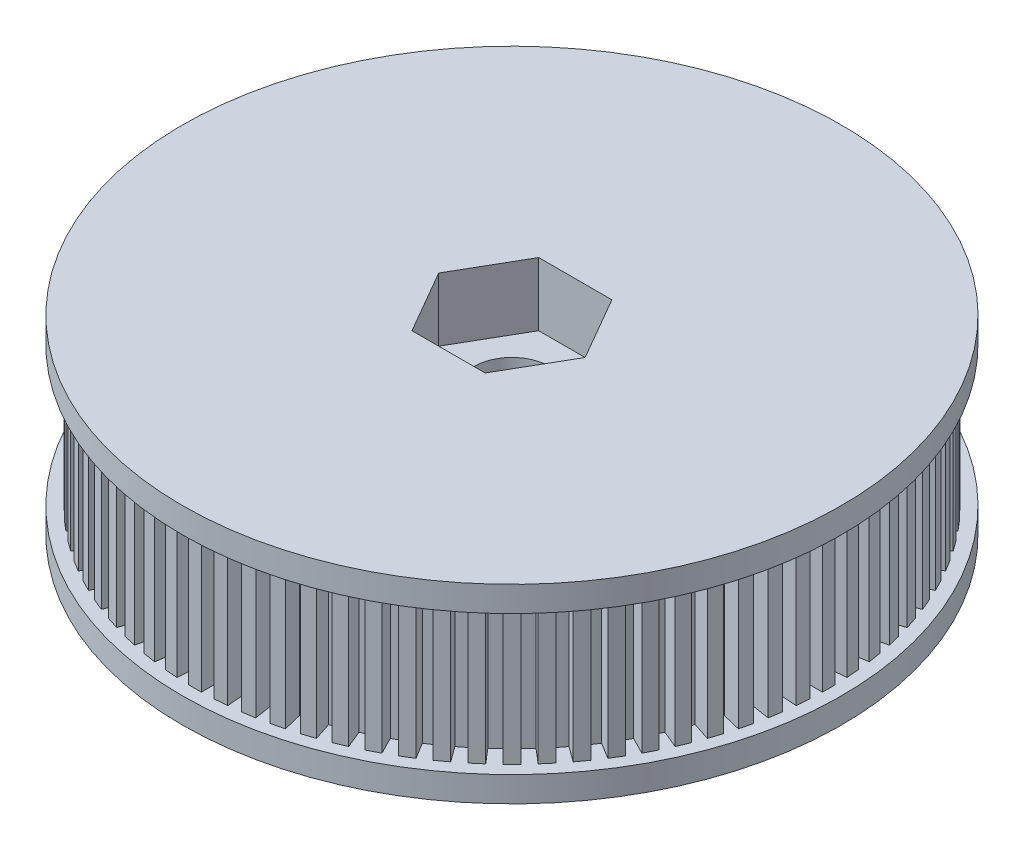
SolidWorks part; units mm, degrees
ref_plane "Front Plane" through (0, 0, 0) normal (0, 0, 1) x (1, 0, 0)
ref_plane "Top Plane" through (0, 0, 0) normal (0, 1, 0) x (1, 0, 0)
ref_plane "Right Plane" through (0, 0, 0) normal (1, 0, 0) x (0, 0, -1)
sketch "Sketch1" plane through (0, 0, 0) normal (0, 1, 0) x (1, 0, 0)
  line L0 (0, 39.6954) -> (0, -43.6583) construction
  line L1 (-0.5, 23.5) -> (-0.5, 25)
  line L2 (-0.5, 25) -> (0.5, 25)
  line L3 (0.5, 25) -> (0.5, 23.5)
  line L4 (1.3453, 23.4668) -> (1.463, 24.9622)
  line L5 (1.463, 24.9622) -> (2.4599, 24.8837)
  line L6 (2.4599, 24.8837) -> (2.3422, 23.3883)
  line L7 (3.1824, 23.2889) -> (3.417, 24.7704)
  line L8 (3.417, 24.7704) -> (4.4047, 24.614)
  line L9 (4.4047, 24.614) -> (4.1701, 23.1325)
  line L10 (4.9998, 22.9674) -> (5.3499, 24.426)
  line L11 (5.3499, 24.426) -> (6.3223, 24.1925)
  line L12 (6.3223, 24.1925) -> (5.9722, 22.734)
  line L13 (6.7864, 22.5043) -> (7.2499, 23.9309)
  line L14 (7.2499, 23.9309) -> (8.201, 23.6219)
  line L15 (8.201, 23.6219) -> (7.7374, 22.1953)
  line L16 (8.5311, 21.9025) -> (9.1051, 23.2883)
  line L17 (9.1051, 23.2883) -> (10.029, 22.9056)
  line L18 (10.029, 22.9056) -> (9.455, 21.5198)
  line L19 (10.2233, 21.1656) -> (10.9043, 22.5022)
  line L20 (10.9043, 22.5022) -> (11.7953, 22.0482)
  line L21 (11.7953, 22.0482) -> (11.1143, 20.7117)
  line L22 (11.8524, 20.2983) -> (12.6361, 21.5773)
  line L23 (12.6361, 21.5773) -> (13.4888, 21.0548)
  line L24 (13.4888, 21.0548) -> (12.705, 19.7758)
  line L25 (13.4084, 19.3058) -> (14.2901, 20.5193)
  line L26 (14.2901, 20.5193) -> (15.0991, 19.9315)
  line L27 (15.0991, 19.9315) -> (14.2175, 18.718)
  line L28 (14.8818, 18.1943) -> (15.856, 19.3349)
  line L29 (15.856, 19.3349) -> (16.6164, 18.6854)
  line L30 (16.6164, 18.6854) -> (15.6422, 17.5448)
  line L31 (16.2635, 16.9706) -> (17.3241, 18.0312)
  line L32 (17.3241, 18.0312) -> (18.0312, 17.3241)
  line L33 (18.0312, 17.3241) -> (16.9706, 16.2635)
  line L34 (17.5448, 15.6422) -> (18.6854, 16.6164)
  line L35 (18.6854, 16.6164) -> (19.3349, 15.856)
  line L36 (19.3349, 15.856) -> (18.1943, 14.8818)
  line L37 (18.718, 14.2175) -> (19.9315, 15.0991)
  line L38 (19.9315, 15.0991) -> (20.5193, 14.2901)
  line L39 (20.5193, 14.2901) -> (19.3058, 13.4084)
  line L40 (19.7758, 12.705) -> (21.0548, 13.4888)
  line L41 (21.0548, 13.4888) -> (21.5773, 12.6361)
  line L42 (21.5773, 12.6361) -> (20.2983, 11.8524)
  line L43 (20.7117, 11.1143) -> (22.0482, 11.7953)
  line L44 (22.0482, 11.7953) -> (22.5022, 10.9043)
  line L45 (22.5022, 10.9043) -> (21.1656, 10.2233)
  line L46 (21.5198, 9.455) -> (22.9056, 10.029)
  line L47 (22.9056, 10.029) -> (23.2883, 9.1051)
  line L48 (23.2883, 9.1051) -> (21.9025, 8.5311)
  line L49 (22.1953, 7.7374) -> (23.6219, 8.201)
  line L50 (23.6219, 8.201) -> (23.9309, 7.2499)
  line L51 (23.9309, 7.2499) -> (22.5043, 6.7864)
  line L52 (22.734, 5.9722) -> (24.1925, 6.3223)
  line L53 (24.1925, 6.3223) -> (24.426, 5.3499)
  line L54 (24.426, 5.3499) -> (22.9674, 4.9998)
  line L55 (23.1325, 4.1701) -> (24.614, 4.4047)
  line L56 (24.614, 4.4047) -> (24.7704, 3.417)
  line L57 (24.7704, 3.417) -> (23.2889, 3.1824)
  line L58 (23.3883, 2.3422) -> (24.8837, 2.4599)
  line L59 (24.8837, 2.4599) -> (24.9622, 1.463)
  line L60 (24.9622, 1.463) -> (23.4668, 1.3453)
  line L61 (23.5, 0.5) -> (25, 0.5)
  line L62 (25, 0.5) -> (25, -0.5)
  line L63 (25, -0.5) -> (23.5, -0.5)
  line L64 (23.4668, -1.3453) -> (24.9622, -1.463)
  line L65 (24.9622, -1.463) -> (24.8837, -2.4599)
  line L66 (24.8837, -2.4599) -> (23.3883, -2.3422)
  line L67 (23.2889, -3.1824) -> (24.7704, -3.417)
  line L68 (24.7704, -3.417) -> (24.614, -4.4047)
  line L69 (24.614, -4.4047) -> (23.1325, -4.1701)
  line L70 (22.9674, -4.9998) -> (24.426, -5.3499)
  line L71 (24.426, -5.3499) -> (24.1925, -6.3223)
  line L72 (24.1925, -6.3223) -> (22.734, -5.9722)
  line L73 (22.5043, -6.7864) -> (23.9309, -7.2499)
  line L74 (23.9309, -7.2499) -> (23.6219, -8.201)
  line L75 (23.6219, -8.201) -> (22.1953, -7.7374)
  line L76 (21.9025, -8.5311) -> (23.2883, -9.1051)
  line L77 (23.2883, -9.1051) -> (22.9056, -10.029)
  line L78 (22.9056, -10.029) -> (21.5198, -9.455)
  line L79 (21.1656, -10.2233) -> (22.5022, -10.9043)
  line L80 (22.5022, -10.9043) -> (22.0482, -11.7953)
  line L81 (22.0482, -11.7953) -> (20.7117, -11.1143)
  line L82 (20.2983, -11.8524) -> (21.5773, -12.6361)
  line L83 (21.5773, -12.6361) -> (21.0548, -13.4888)
  line L84 (21.0548, -13.4888) -> (19.7758, -12.705)
  line L85 (19.3058, -13.4084) -> (20.5193, -14.2901)
  line L86 (20.5193, -14.2901) -> (19.9315, -15.0991)
  line L87 (19.9315, -15.0991) -> (18.718, -14.2175)
  line L88 (18.1943, -14.8818) -> (19.3349, -15.856)
  line L89 (19.3349, -15.856) -> (18.6854, -16.6164)
  line L90 (18.6854, -16.6164) -> (17.5448, -15.6422)
  line L91 (16.9706, -16.2635) -> (18.0312, -17.3241)
  line L92 (18.0312, -17.3241) -> (17.3241, -18.0312)
  line L93 (17.3241, -18.0312) -> (16.2635, -16.9706)
  line L94 (15.6422, -17.5448) -> (16.6164, -18.6854)
  line L95 (16.6164, -18.6854) -> (15.856, -19.3349)
  line L96 (15.856, -19.3349) -> (14.8818, -18.1943)
  line L97 (14.2175, -18.718) -> (15.0991, -19.9315)
  line L98 (15.0991, -19.9315) -> (14.2901, -20.5193)
  line L99 (14.2901, -20.5193) -> (13.4084, -19.3058)
  line L100 (12.705, -19.7758) -> (13.4888, -21.0548)
  line L101 (13.4888, -21.0548) -> (12.6361, -21.5773)
  line L102 (12.6361, -21.5773) -> (11.8524, -20.2983)
  line L103 (11.1143, -20.7117) -> (11.7953, -22.0482)
  line L104 (11.7953, -22.0482) -> (10.9043, -22.5022)
  line L105 (10.9043, -22.5022) -> (10.2233, -21.1656)
  line L106 (9.455, -21.5198) -> (10.029, -22.9056)
  line L107 (10.029, -22.9056) -> (9.1051, -23.2883)
  line L108 (9.1051, -23.2883) -> (8.5311, -21.9025)
  line L109 (7.7374, -22.1953) -> (8.201, -23.6219)
  line L110 (8.201, -23.6219) -> (7.2499, -23.9309)
  line L111 (7.2499, -23.9309) -> (6.7864, -22.5043)
  line L112 (5.9722, -22.734) -> (6.3223, -24.1925)
  line L113 (6.3223, -24.1925) -> (5.3499, -24.426)
  line L114 (5.3499, -24.426) -> (4.9998, -22.9674)
  line L115 (4.1701, -23.1325) -> (4.4047, -24.614)
  line L116 (4.4047, -24.614) -> (3.417, -24.7704)
  line L117 (3.417, -24.7704) -> (3.1824, -23.2889)
  line L118 (2.3422, -23.3883) -> (2.4599, -24.8837)
  line L119 (2.4599, -24.8837) -> (1.463, -24.9622)
  line L120 (1.463, -24.9622) -> (1.3453, -23.4668)
  line L121 (0.5, -23.5) -> (0.5, -25)
  line L122 (0.5, -25) -> (-0.5, -25)
  line L123 (-0.5, -25) -> (-0.5, -23.5)
  line L124 (-1.3453, -23.4668) -> (-1.463, -24.9622)
  line L125 (-1.463, -24.9622) -> (-2.4599, -24.8837)
  line L126 (-2.4599, -24.8837) -> (-2.3422, -23.3883)
  line L127 (-3.1824, -23.2889) -> (-3.417, -24.7704)
  line L128 (-3.417, -24.7704) -> (-4.4047, -24.614)
  line L129 (-4.4047, -24.614) -> (-4.1701, -23.1325)
  line L130 (-4.9998, -22.9674) -> (-5.3499, -24.426)
  line L131 (-5.3499, -24.426) -> (-6.3223, -24.1925)
  line L132 (-6.3223, -24.1925) -> (-5.9722, -22.734)
  line L133 (-6.7864, -22.5043) -> (-7.2499, -23.9309)
  line L134 (-7.2499, -23.9309) -> (-8.201, -23.6219)
  line L135 (-8.201, -23.6219) -> (-7.7374, -22.1953)
  line L136 (-8.5311, -21.9025) -> (-9.1051, -23.2883)
  line L137 (-9.1051, -23.2883) -> (-10.029, -22.9056)
  line L138 (-10.029, -22.9056) -> (-9.455, -21.5198)
  line L139 (-10.2233, -21.1656) -> (-10.9043, -22.5022)
  line L140 (-10.9043, -22.5022) -> (-11.7953, -22.0482)
  line L141 (-11.7953, -22.0482) -> (-11.1143, -20.7117)
  line L142 (-11.8524, -20.2983) -> (-12.6361, -21.5773)
  line L143 (-12.6361, -21.5773) -> (-13.4888, -21.0548)
  line L144 (-13.4888, -21.0548) -> (-12.705, -19.7758)
  line L145 (-13.4084, -19.3058) -> (-14.2901, -20.5193)
  line L146 (-14.2901, -20.5193) -> (-15.0991, -19.9315)
  line L147 (-15.0991, -19.9315) -> (-14.2175, -18.718)
  line L148 (-14.8818, -18.1943) -> (-15.856, -19.3349)
  line L149 (-15.856, -19.3349) -> (-16.6164, -18.6854)
  line L150 (-16.6164, -18.6854) -> (-15.6422, -17.5448)
  line L151 (-16.2635, -16.9706) -> (-17.3241, -18.0312)
  line L152 (-17.3241, -18.0312) -> (-18.0312, -17.3241)
  line L153 (-18.0312, -17.3241) -> (-16.9706, -16.2635)
  line L154 (-17.5448, -15.6422) -> (-18.6854, -16.6164)
  line L155 (-18.6854, -16.6164) -> (-19.3349, -15.856)
  line L156 (-19.3349, -15.856) -> (-18.1943, -14.8818)
  line L157 (-18.718, -14.2175) -> (-19.9315, -15.0991)
  line L158 (-19.9315, -15.0991) -> (-20.5193, -14.2901)
  line L159 (-20.5193, -14.2901) -> (-19.3058, -13.4084)
  line L160 (-19.7758, -12.705) -> (-21.0548, -13.4888)
  line L161 (-21.0548, -13.4888) -> (-21.5773, -12.6361)
  line L162 (-21.5773, -12.6361) -> (-20.2983, -11.8524)
  line L163 (-20.7117, -11.1143) -> (-22.0482, -11.7953)
  line L164 (-22.0482, -11.7953) -> (-22.5022, -10.9043)
  line L165 (-22.5022, -10.9043) -> (-21.1656, -10.2233)
  line L166 (-21.5198, -9.455) -> (-22.9056, -10.029)
  line L167 (-22.9056, -10.029) -> (-23.2883, -9.1051)
  line L168 (-23.2883, -9.1051) -> (-21.9025, -8.5311)
  line L169 (-22.1953, -7.7374) -> (-23.6219, -8.201)
  line L170 (-23.6219, -8.201) -> (-23.9309, -7.2499)
  line L171 (-23.9309, -7.2499) -> (-22.5043, -6.7864)
  line L172 (-22.734, -5.9722) -> (-24.1925, -6.3223)
  line L173 (-24.1925, -6.3223) -> (-24.426, -5.3499)
  line L174 (-24.426, -5.3499) -> (-22.9674, -4.9998)
  line L175 (-23.1325, -4.1701) -> (-24.614, -4.4047)
  line L176 (-24.614, -4.4047) -> (-24.7704, -3.417)
  line L177 (-24.7704, -3.417) -> (-23.2889, -3.1824)
  line L178 (-23.3883, -2.3422) -> (-24.8837, -2.4599)
  line L179 (-24.8837, -2.4599) -> (-24.9622, -1.463)
  line L180 (-24.9622, -1.463) -> (-23.4668, -1.3453)
  line L181 (-23.5, -0.5) -> (-25, -0.5)
  line L182 (-25, -0.5) -> (-25, 0.5)
  line L183 (-25, 0.5) -> (-23.5, 0.5)
  line L184 (-23.4668, 1.3453) -> (-24.9622, 1.463)
  line L185 (-24.9622, 1.463) -> (-24.8837, 2.4599)
  line L186 (-24.8837, 2.4599) -> (-23.3883, 2.3422)
  line L187 (-23.2889, 3.1824) -> (-24.7704, 3.417)
  line L188 (-24.7704, 3.417) -> (-24.614, 4.4047)
  line L189 (-24.614, 4.4047) -> (-23.1325, 4.1701)
  line L190 (-22.9674, 4.9998) -> (-24.426, 5.3499)
  line L191 (-24.426, 5.3499) -> (-24.1925, 6.3223)
  line L192 (-24.1925, 6.3223) -> (-22.734, 5.9722)
  line L193 (-22.5043, 6.7864) -> (-23.9309, 7.2499)
  line L194 (-23.9309, 7.2499) -> (-23.6219, 8.201)
  line L195 (-23.6219, 8.201) -> (-22.1953, 7.7374)
  line L196 (-21.9025, 8.5311) -> (-23.2883, 9.1051)
  line L197 (-23.2883, 9.1051) -> (-22.9056, 10.029)
  line L198 (-22.9056, 10.029) -> (-21.5198, 9.455)
  line L199 (-21.1656, 10.2233) -> (-22.5022, 10.9043)
  line L200 (-22.5022, 10.9043) -> (-22.0482, 11.7953)
  line L201 (-22.0482, 11.7953) -> (-20.7117, 11.1143)
  line L202 (-20.2983, 11.8524) -> (-21.5773, 12.6361)
  line L203 (-21.5773, 12.6361) -> (-21.0548, 13.4888)
  line L204 (-21.0548, 13.4888) -> (-19.7758, 12.705)
  line L205 (-19.3058, 13.4084) -> (-20.5193, 14.2901)
  line L206 (-20.5193, 14.2901) -> (-19.9315, 15.0991)
  line L207 (-19.9315, 15.0991) -> (-18.718, 14.2175)
  line L208 (-18.1943, 14.8818) -> (-19.3349, 15.856)
  line L209 (-19.3349, 15.856) -> (-18.6854, 16.6164)
  line L210 (-18.6854, 16.6164) -> (-17.5448, 15.6422)
  line L211 (-16.9706, 16.2635) -> (-18.0312, 17.3241)
  line L212 (-18.0312, 17.3241) -> (-17.3241, 18.0312)
  line L213 (-17.3241, 18.0312) -> (-16.2635, 16.9706)
  line L214 (-15.6422, 17.5448) -> (-16.6164, 18.6854)
  line L215 (-16.6164, 18.6854) -> (-15.856, 19.3349)
  line L216 (-15.856, 19.3349) -> (-14.8818, 18.1943)
  line L217 (-14.2175, 18.718) -> (-15.0991, 19.9315)
  line L218 (-15.0991, 19.9315) -> (-14.2901, 20.5193)
  line L219 (-14.2901, 20.5193) -> (-13.4084, 19.3058)
  line L220 (-12.705, 19.7758) -> (-13.4888, 21.0548)
  line L221 (-13.4888, 21.0548) -> (-12.6361, 21.5773)
  line L222 (-12.6361, 21.5773) -> (-11.8524, 20.2983)
  line L223 (-11.1143, 20.7117) -> (-11.7953, 22.0482)
  line L224 (-11.7953, 22.0482) -> (-10.9043, 22.5022)
  line L225 (-10.9043, 22.5022) -> (-10.2233, 21.1656)
  line L226 (-9.455, 21.5198) -> (-10.029, 22.9056)
  line L227 (-10.029, 22.9056) -> (-9.1051, 23.2883)
  line L228 (-9.1051, 23.2883) -> (-8.5311, 21.9025)
  line L229 (-7.7374, 22.1953) -> (-8.201, 23.6219)
  line L230 (-8.201, 23.6219) -> (-7.2499, 23.9309)
  line L231 (-7.2499, 23.9309) -> (-6.7864, 22.5043)
  line L232 (-5.9722, 22.734) -> (-6.3223, 24.1925)
  line L233 (-6.3223, 24.1925) -> (-5.3499, 24.426)
  line L234 (-5.3499, 24.426) -> (-4.9998, 22.9674)
  line L235 (-4.1701, 23.1325) -> (-4.4047, 24.614)
  line L236 (-4.4047, 24.614) -> (-3.417, 24.7704)
  line L237 (-3.417, 24.7704) -> (-3.1824, 23.2889)
  line L238 (-2.3422, 23.3883) -> (-2.4599, 24.8837)
  line L239 (-2.4599, 24.8837) -> (-1.463, 24.9622)
  line L240 (-1.463, 24.9622) -> (-1.3453, 23.4668)
  line L242 (-2.8868, 5) -> (-5.7735, 0)
  line L243 (-5.7735, 0) -> (-2.8868, -5)
  line L244 (-2.8868, -5) -> (2.8868, -5)
  line L245 (2.8868, -5) -> (5.7735, 0)
  line L246 (5.7735, 0) -> (2.8868, 5)
  line L247 (2.8868, 5) -> (-2.8868, 5)
  circle A0 centre (0, 0) radius 26
  circle A1 centre (0, 0) radius 23.5053
  circle A2 centre (0, 0) radius 3
  circle A3 centre (0, 0) radius 5 construction
  point P329 (0, 0)
  dimension "D1" = 52
  dimension "D6" = 6
  dimension "D2" = 1
  dimension "D3" = 1.5
  dimension "D4" = 25
  dimension "D7" = 10
  dimension "D5" = 80
extrude "Boss-Extrude1" add sketch "Sketch1" along normal blind 15 contours A1 L240 L239 L238 | A1 L237 L236 L235 | A1 L234 L233 L232 | A1 L231 L230 L229 | A1 L228 L227 L226 | A1 L225 L224 L223 | A1 L222 L221 L220 | A1 L219 L218 L217 | A1 L216 L215 L214 | A1 L213 L212 L211 | A1 L210 L209 L208 | A1 L207 L206 L205 | A1 L204 L203 L202 | A1 L201 L200 L199 | A1 L198 L197 L196 | A1 L195 L194 L193 | A1 L192 L191 L190 | A1 L189 L188 L187 | A1 L186 L185 L184 | A1 L183 L182 L181 | A1 L180 L179 L178 | A1 L177 L176 L175 | A1 L174 L173 L172 | A1 L171 L170 L169 | A1 L168 L167 L166 | A1 L165 L164 L163 | A1 L162 L161 L160 | A1 L159 L158 L157 | A1 L156 L155 L154 | A1 L153 L152 L151 | A1 L150 L149 L148 | A1 L147 L146 L145 | A1 L144 L143 L142 | A1 L141 L140 L139 | A1 L138 L137 L136 | A1 L135 L134 L133 | A1 L132 L131 L130 | A1 L129 L128 L127 | A1 L126 L125 L124 | A1 L120 L119 L118 | A1 L117 L116 L115 | A1 L114 L113 L112 | A1 L111 L110 L109 | A1 L108 L107 L106 | A1 L105 L104 L103 | A1 L102 L101 L100 | A1 L99 L98 L97 | A1 L96 L95 L94 | A1 L93 L92 L91 | A1 L90 L89 L88 | A1 L87 L86 L85 | A1 L84 L83 L82 | A1 L81 L80 L79 | A1 L78 L77 L76 | A1 L75 L74 L73 | A1 L72 L71 L70 | A1 L69 L68 L67 | A1 L66 L65 L64 | A1 L63 L62 L61 | A1 L60 L59 L58 | A1 L57 L56 L55 | A1 L54 L53 L52 | A1 L51 L50 L49 | A1 L48 L47 L46 | A1 L45 L44 L43 | A1 L42 L41 L40 | A1 L39 L38 L37 | A1 L36 L35 L34 | A1 L33 L32 L31 | A1 L30 L29 L28 | A1 L27 L26 L25 | A1 L24 L23 L22 | A1 L21 L20 L19 | A1 L18 L17 L16 | A1 L15 L14 L13 | A1 L12 L11 L10 | A1 L9 L8 L7 | A1 L6 L5 L4 | A1 L3 L2 L1 | A1 L123 L122 L121 | A1 | L246 L247 L242 L243 L244 L245 A2 region at (0, 0, -24.2518) region at (0, 0, -22.8405) region at (-1.9028, 0, -24.177) region at (1.9028, 0, -24.177) region at (-3.7938, 0, -23.9532) region at (3.7938, 0, -23.9532) region at (-5.6615, 0, -23.5817) region at (5.6615, 0, -23.5817) region at (-7.4942, 0, -23.0648) region at (7.4942, 0, -23.0648) region at (-9.2808, 0, -22.4057) region at (9.2808, 0, -22.4057) region at (-11.0101, 0, -21.6085) region at (11.0101, 0, -21.6085) region at (-12.6715, 0, -20.678) region at (12.6715, 0, -20.678) region at (-14.2548, 0, -19.6201) region at (14.2548, 0, -19.6201) region at (-15.7503, 0, -18.4412) region at (15.7503, 0, -18.4412) region at (-17.1486, 0, -17.1486) region at (17.1486, 0, -17.1486) region at (-18.4412, 0, -15.7503) region at (18.4412, 0, -15.7503) region at (-19.6201, 0, -14.2548) region at (19.6201, 0, -14.2548) region at (-20.678, 0, -12.6715) region at (20.678, 0, -12.6715) region at (-21.6085, 0, -11.0101) region at (21.6085, 0, -11.0101) region at (-22.4057, 0, -9.2808) region at (22.4057, 0, -9.2808) region at (-23.0648, 0, -7.4942) region at (23.0648, 0, -7.4942) region at (-23.5817, 0, -5.6615) region at (23.5817, 0, -5.6615) region at (-23.9532, 0, -3.7938) region at (23.9532, 0, -3.7938) region at (-24.177, 0, -1.9028) region at (24.177, 0, -1.9028) region at (-24.2518, 0, 0) region at (24.2518, 0, 0) region at (-24.177, 0, 1.9028) region at (24.177, 0, 1.9028) region at (-23.9532, 0, 3.7938) region at (23.9532, 0, 3.7938) region at (-23.5817, 0, 5.6615) region at (23.5817, 0, 5.6615) region at (-23.0648, 0, 7.4942) region at (23.0648, 0, 7.4942) region at (-22.4057, 0, 9.2808) region at (22.4057, 0, 9.2808) region at (-21.6085, 0, 11.0101) region at (21.6085, 0, 11.0101) region at (-20.678, 0, 12.6715) region at (20.678, 0, 12.6715) region at (-19.6201, 0, 14.2548) region at (19.6201, 0, 14.2548) region at (-18.4412, 0, 15.7503) region at (18.4412, 0, 15.7503)
extrude "Boss-Extrude2" add sketch "Sketch1<3>" along normal blind 2 contours A0 A1 L121 L122 L123 L124 L125 L126 L127 L128 L129 L130 L131 L132 L133 L134 L135 L136 L137 L138 L139 L140 L141 L142 L143 L144 L145 L146 L147 L148 L149 L150 L151 L152 L153 L154 L155 L156 region at (-25.2646, 0, 0)
sketch "Sketch1<3>" plane through (0, 0, 0) normal (0, 1, 0) x (1, 0, 0) same geometry as "Sketch1"
extrude "Boss-Extrude3" add sketch "Sketch1<4>" against normal blind 2 from surface contours A0 A1 L121 L122 L123 L124 L125 L126 L127 L128 L129 L130 L131 L132 L133 L134 L135 L136 L137 L138 L139 L140 L141 L142 L143 L144 L145 L146 L147 L148 L149 L150 L151 L152 L153 L154 L155 L156 region at (-25.2646, 0, 0) starting at face at (0, 15, 0)
sketch "Sketch1<4>" plane through (0, 0, 0) normal (0, 1, 0) x (1, 0, 0) same geometry as "Sketch1"
extrude "Cut-Extrude1" cut sketch "Sketch1<5>" against normal blind 5 from surface contours L246 L247 L242 L243 L244 L245 A2 region at (0, 0, -4.8472) starting at face at (0, 15, 3)
sketch "Sketch1<5>" plane through (0, 0, 0) normal (0, 1, 0) x (1, 0, 0) same geometry as "Sketch1"
